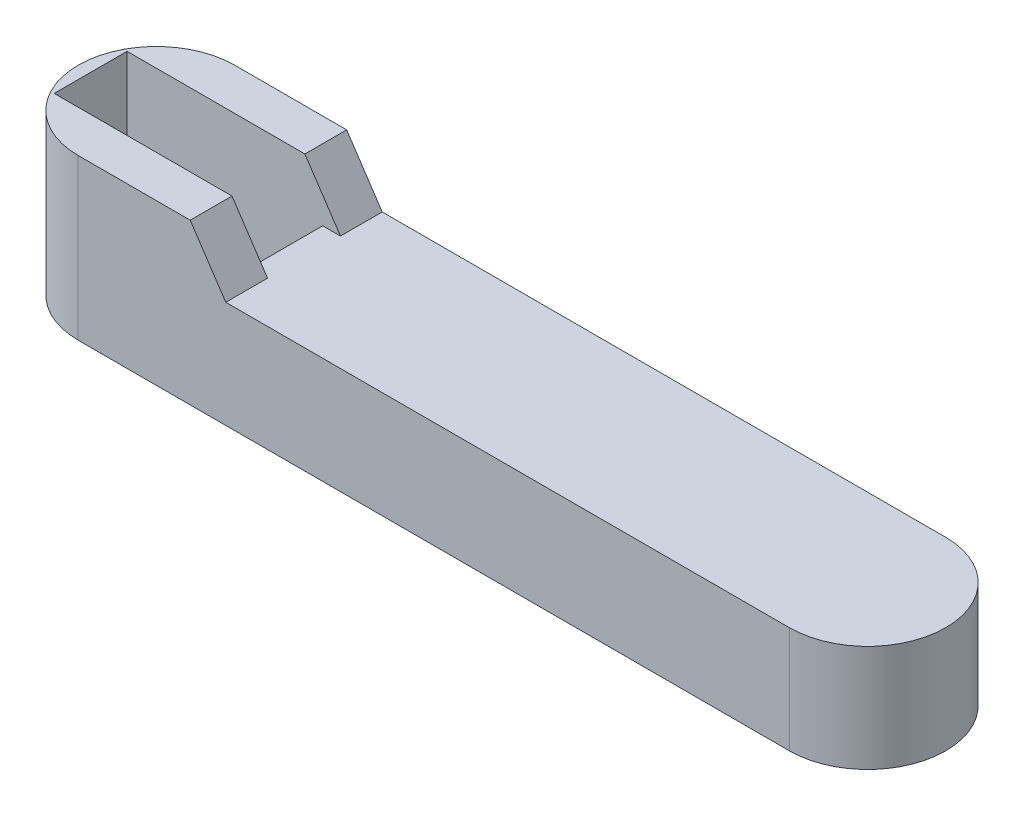
SolidWorks part; units mm, degrees
ref_plane "Front Plane" through (0, 0, 0) normal (0, 0, 1) x (1, 0, 0)
ref_plane "Top Plane" through (0, 0, 0) normal (0, 1, 0) x (1, 0, 0)
ref_plane "Right Plane" through (0, 0, 0) normal (1, 0, 0) x (0, 0, -1)
sketch "Sketch1" plane through (0, 0, 0) normal (0, 1, 0) x (1, 0, 0)
  line L0 (0, 0) -> (200, 0)
  line L1 (0, 44) -> (200, 44)
  arc A0 (0, 0) -> (0, 44) centre (0, 22) cw
  arc A1 (200, 44) -> (200, 0) centre (200, 22) cw
  dimension "D2" = 22
  dimension "D1" = 200
extrude "Boss-Extrude1" add sketch "Sketch1" along normal blind 30
sketch "Sketch2" plane through (0, 30, 0) normal (0, 1, 0) x (1, 0, 0)
  line L0 (0, 44) -> (0, 0) construction
  circle A0 centre (0, 22) radius 7
  arc A1 (0, 44) -> (0, 0) centre (0, 22) ccw construction
  point P8 (0, 22)
  dimension "D1" = 14
extrude "Cut-Extrude1" cut sketch "Sketch2" against normal through all
sketch "Sketch3" plane through (0, 30, 0) normal (0, 1, 0) x (1, 0, 0)
  line L0 (0, 44) -> (0, 0) construction
  line L1 (0, 32.25) -> (-18.5, 32.25)
  line L2 (-18.5, 32.25) -> (-18.5, 11.75)
  line L3 (-18.5, 11.75) -> (0, 11.75)
  line L4 (0, 11.75) -> (36.5, 11.75)
  line L5 (36.5, 11.75) -> (36.5, 32.25)
  line L6 (36.5, 32.25) -> (0, 32.25)
  arc A0 (0, 44) -> (0, 0) centre (0, 22) ccw construction
  point P8 (0, 22)
  point P13 (-18.5, 22)
  dimension "D1" = 20.5
  dimension "D2" = 18.5
  dimension "D3" = 36.5
extrude "Cut-Extrude2" cut sketch "Sketch3" against normal blind 28.5
sketch "Sketch5" plane through (0, 30, 0) normal (0, 1, 0) x (1, 0, 0)
  line L0 (-18.5, 32.25) -> (-18.5, 11.75)
  line L1 (-18.5, 11.75) -> (41.5, 11.75)
  line L3 (41.5, 32.25) -> (-18.5, 32.25)
  line L4 (0, 44) -> (41.5, 44)
  line L5 (200, 44) -> (0, 44) construction
  line L8 (0, 0) -> (200, 0) construction
  line L9 (41.5, 0) -> (0, 0)
  line L10 (41.5, 44) -> (41.5, 32.25)
  line L11 (41.5, 0) -> (41.5, 11.75)
  line L12 (36.5, 11.75) -> (36.5, 32.25) construction
  arc A0 (0, 44) -> (0, 0) centre (0, 22) ccw
  point P5 (42.2086, 0)
  point P7 (42.2086, 44)
  point P14 (42.1178, 32.25)
  point P23 (42.2086, 11.75)
  dimension "D1" = 5
extrude "Boss-Extrude2" add sketch "Sketch5" along normal blind 15
sketch "Sketch6" plane through (0, 0, 0) normal (0, 0, 1) x (1, 0, 0)
  line L0 (31.5, 45) -> (41.5, 45)
  line L1 (0, 45) -> (41.5, 45) construction
  line L2 (41.5, 45) -> (41.5, 30)
  line L3 (41.5, 30) -> (31.5, 45)
  dimension "D1" = 10
extrude "Cut-Extrude3" cut sketch "Sketch6" against normal through all
